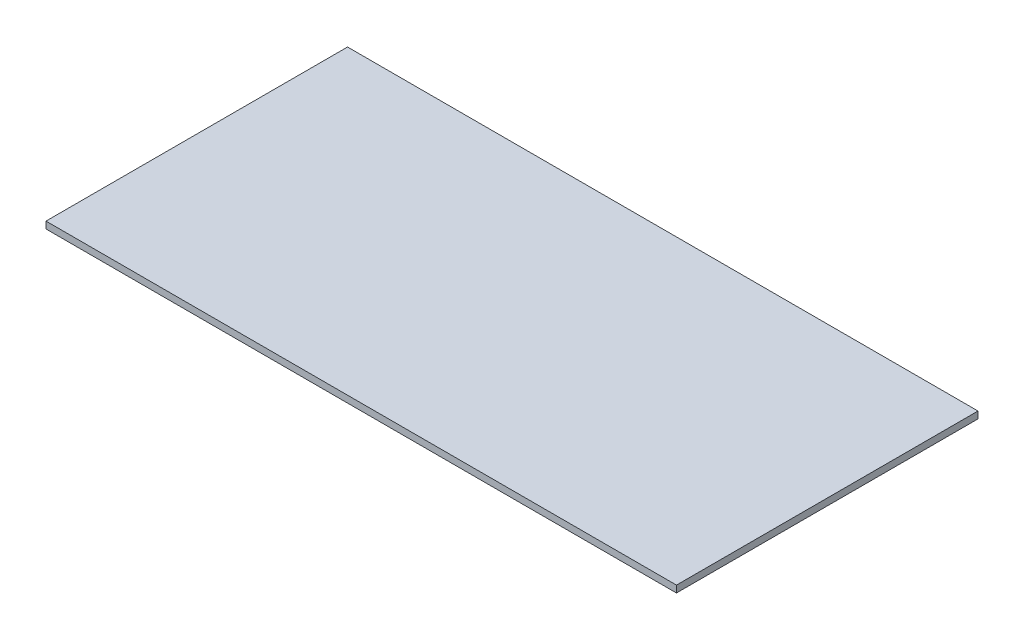
SolidWorks part; units mm, degrees
material "Acrylic (Medium-high impact)"
ref_plane "Front Plane" through (0, 0, 0) normal (0, 0, 1) x (1, 0, 0)
ref_plane "Top Plane" through (0, 0, 0) normal (0, 1, 0) x (1, 0, 0)
ref_plane "Right Plane" through (0, 0, 0) normal (1, 0, 0) x (0, 0, -1)
sketch "Sketch1" plane through (0, 0, 0) normal (0, 1, 0) x (1, 0, 0)
  line L1 (-292.1, 139.7) -> (292.1, 139.7)
  line L2 (-292.1, 139.7) -> (-292.1, -139.7)
  line L3 (-292.1, -139.7) -> (292.1, -139.7)
  line L4 (292.1, 139.7) -> (292.1, -139.7)
  line L5 (-292.1, 139.7) -> (292.1, -139.7) construction
  line L6 (-292.1, -139.7) -> (292.1, 139.7) construction
  point P4 (0, 0)
  point P5 (0, 0)
  dimension "D1" = 279.4
  dimension "D2" = 584.2
extrude "Baseplate" add sketch "Sketch1" along normal blind 6.35
sketch "Mounting Points" plane through (0, 6.35, 0) normal (0, 1, 0) x (1, 0, 0)
  line L0 (-292.1, -127) -> (292.1, -127) construction
  line L1 (-292.1, 139.7) -> (-292.1, -139.7) construction
  line L2 (292.1, -139.7) -> (292.1, 139.7) construction
  line L3 (-292.1, -139.7) -> (292.1, -139.7) construction
  line L4 (-55, 0) -> (55, 0) construction
  line L5 (-292.1, 127) -> (292.1, 127) construction
  point P8 (133.35, -127)
  point P9 (-240.5126, -127)
  point P10 (-19.05, -127)
  point P11 (-69.85, -127)
  point P20 (-69.85, 127)
  point P21 (-19.05, 127)
  point P22 (-240.5126, 127)
  point P23 (133.35, 127)
  dimension "D1" = 12.7
  dimension "D2" = 158.75
  dimension "D3" = 50.8
  dimension "D4" = 152.4
  dimension "D5" = 170.6626
sketch "Battery Adaptors" plane through (0, 6.35, 0) normal (0, 1, 0) x (1, 0, 0)
  line L0 (208.4146, -118.6932) -> (290.6217, -118.6932) construction
  line L1 (208.4146, -118.6932) -> (208.4146, -20.2682) construction
  line L2 (208.4146, -20.2682) -> (290.6217, -20.2682) construction
  line L3 (290.6217, -118.6932) -> (290.6217, -20.2682) construction
  line L8 (121.1275, -118.6932) -> (203.3346, -118.6932) construction
  line L9 (121.1275, -118.6932) -> (121.1275, -20.2682) construction
  line L10 (121.1275, -20.2682) -> (203.3346, -20.2682) construction
  line L11 (203.3346, -118.6932) -> (203.3346, -20.2682) construction
  point P0 (215.3646, -25.6682)
  point P5 (283.6717, -25.6682)
  point P6 (269.3117, -113.2932)
  point P7 (229.7246, -113.2932)
  point P14 (128.0775, -25.6682)
  point P19 (196.3846, -25.6682)
  point P20 (182.0246, -113.2932)
  point P21 (142.4375, -113.2932)
  dimension "D1" = 98.425
  dimension "D2" = 82.2071
  dimension "D3" = 5.4
  dimension "D4" = 5.4
  dimension "D5" = 6.95
  dimension "D6" = 6.95
  dimension "D7" = 21.31
  dimension "D8" = 21.31
  dimension "D11" = 98.425
  dimension "D12" = 82.2071
  dimension "D13" = 6.95
  dimension "D14" = 6.95
  dimension "D15" = 21.31
  dimension "D16" = 21.31
  dimension "D17" = 5.08
sketch "Orin Nano" plane through (0, 6.35, 0) normal (0, 1, 0) x (1, 0, 0)
  line L1 (95.1261, 101.2046) -> (209.4261, 101.2046) construction
  line L2 (95.1261, 101.2046) -> (95.1261, -1.6654) construction
  line L3 (95.1261, -1.6654) -> (209.4261, -1.6654) construction
  line L4 (209.4261, 101.2046) -> (209.4261, -1.6654) construction
  point P4 (98.9361, 97.3946)
  point P5 (205.6161, 97.3946)
  point P6 (205.6161, 2.1446)
  point P7 (98.9361, 2.1446)
  dimension "D1" = 102.87
  dimension "D2" = 114.3
  dimension "D3" = 3.81
  dimension "D4" = 3.81
  dimension "D5" = 3.81
  dimension "D6" = 3.81
sketch "Air Tank Shadow" plane through (0, 6.35, 0) normal (0, 1, 0) x (1, 0, 0)
  line L1 (-342.6787, 115.7653) -> (-182.6587, 115.7653) construction
  line L2 (-342.6787, 115.7653) -> (-342.6787, -23.9347) construction
  line L3 (-342.6787, -23.9347) -> (-182.6587, -23.9347) construction
  line L4 (-182.6587, 115.7653) -> (-182.6587, -23.9347) construction
  line L5 (-342.6787, 115.7653) -> (-182.6587, -23.9347) construction
  line L6 (-342.6787, -23.9347) -> (-182.6587, 115.7653) construction
  point P4 (-262.6687, 45.9153)
  dimension "D1" = 160.02
  dimension "D2" = 139.7
sketch "Router Shadow" plane through (0, 6.35, 0) normal (0, 1, 0) x (1, 0, 0)
  line L1 (-192.9184, 98.6941) -> (-65.9184, 98.6941) construction
  line L2 (-192.9184, 98.6941) -> (-192.9184, -104.5059) construction
  line L3 (-192.9184, -104.5059) -> (-65.9184, -104.5059) construction
  line L4 (-65.9184, 98.6941) -> (-65.9184, -104.5059) construction
  line L5 (-192.9184, 98.6941) -> (-65.9184, -104.5059) construction
  line L6 (-192.9184, -104.5059) -> (-65.9184, 98.6941) construction
  point P4 (-129.4184, -2.9059)
  dimension "D1" = 203.2
  dimension "D2" = 127
sketch "PCB Mount" plane through (0, 6.35, 0) normal (0, 1, 0) x (1, 0, 0)
  line L1 (-60.8861, 132.0384) -> (85.1639, 132.0384) construction
  line L2 (-60.8861, 132.0384) -> (-60.8861, -14.0116) construction
  line L3 (-60.8861, -14.0116) -> (85.1639, -14.0116) construction
  line L4 (85.1639, 132.0384) -> (85.1639, -14.0116) construction
  line L5 (-60.8861, 132.0384) -> (85.1639, -14.0116) construction
  line L6 (-60.8861, -14.0116) -> (85.1639, 132.0384) construction
  point P4 (12.1389, 59.0134)
  dimension "D1" = 146.05
  dimension "D2" = 146.05
sketch "Power Distribution" plane through (0, 6.35, 0) normal (0, 1, 0) x (1, 0, 0)
  line L1 (105.2134, -158.0614) -> (232.2134, -158.0614) construction
  line L2 (105.2134, -158.0614) -> (105.2134, -196.1614) construction
  line L3 (105.2134, -196.1614) -> (232.2134, -196.1614) construction
  line L4 (232.2134, -158.0614) -> (232.2134, -196.1614) construction
  line L5 (105.2134, -158.0614) -> (232.2134, -196.1614) construction
  line L6 (105.2134, -196.1614) -> (232.2134, -158.0614) construction
  point P4 (168.7134, -177.1114)
  dimension "D1" = 38.1
  dimension "D2" = 127
sketch "Voltage Regulators" plane through (0, 6.35, 0) normal (0, 1, 0) x (1, 0, 0)
  line L1 (-52.1195, -25.3804) -> (81.2305, -25.3804) construction
  line L2 (-52.1195, -25.3804) -> (-52.1195, -126.9804) construction
  line L3 (-52.1195, -126.9804) -> (81.2305, -126.9804) construction
  line L4 (81.2305, -25.3804) -> (81.2305, -126.9804) construction
  line L5 (-52.1195, -25.3804) -> (81.2305, -126.9804) construction
  line L6 (-52.1195, -126.9804) -> (81.2305, -25.3804) construction
  point P4 (14.5555, -76.1804)
  dimension "D1" = 133.35
  dimension "D2" = 101.6
sketch "Stepper Driver" plane through (0, 6.35, 0) normal (0, 1, 0) x (1, 0, 0)
  line L1 (198.5846, 111.6277) -> (287.4846, 111.6277) construction
  line L2 (198.5846, 111.6277) -> (198.5846, -2.6723) construction
  line L3 (198.5846, -2.6723) -> (287.4846, -2.6723) construction
  line L4 (287.4846, 111.6277) -> (287.4846, -2.6723) construction
  line L5 (198.5846, 111.6277) -> (287.4846, -2.6723) construction
  line L6 (198.5846, -2.6723) -> (287.4846, 111.6277) construction
  point P4 (243.0346, 54.4777)
  dimension "D1" = 88.9
  dimension "D2" = 114.3
